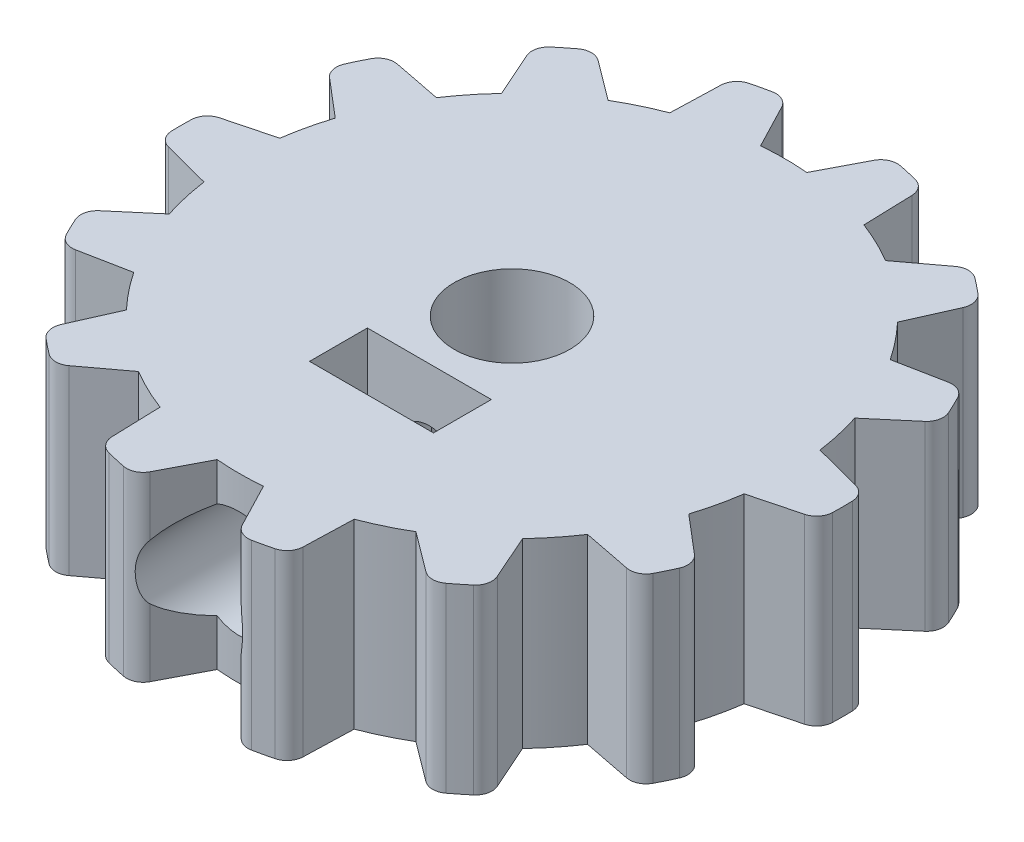
SolidWorks part; units mm, degrees
ref_plane "Front Plane" through (0, 0, 0) normal (0, 0, 1) x (1, 0, 0)
ref_plane "Top Plane" through (0, 0, 0) normal (0, 1, 0) x (1, 0, 0)
ref_plane "Right Plane" through (0, 0, 0) normal (1, 0, 0) x (0, 0, -1)
sketch "Sketch1" plane through (0, 0, 0) normal (0, 1, 0) x (1, 0, 0)
  circle A0 centre (0, 0) radius 20
  dimension "D1" = 40
extrude "Boss-Extrude1" add sketch "Sketch1" along normal blind 11
sketch "Sketch2" plane through (0, 11, 0) normal (0, 1, 0) x (1, 0, 0)
  line L0 (-3.125, 19.7544) -> (-1.3999, 16.4405)
  line L2 (1.3999, 16.4405) -> (3.125, 19.7544)
  circle A0 centre (0, 0) radius 20 construction
  arc A1 (-1.3999, 16.4405) -> (1.3999, 16.4405) centre (0, 0) cw
  arc A2 (3.125, 19.7544) -> (-3.125, 19.7544) centre (0, 0) ccw
  point P6 (0, 16.5)
  dimension "D1" = 16.5
  dimension "D2" = 55
  dimension "D3" = 6.25
extrude "Cut-Extrude1" cut sketch "Sketch2" against normal up to next
fillet "Fillet1" radius 1 2 edges at (3.125, 5.5, -19.7544) (-3.125, 5.5, -19.7544)
pattern_circular "CirPattern1" count 14 over 360 about axis through (0, 11, 0) along (0, -1, 0) of "Cut-Extrude1", "Fillet1"
sketch "Sketch3" plane through (0, 11, 0) normal (0, 1, 0) x (1, 0, 0)
  circle A0 centre (0, 0) radius 3.5
  dimension "D1" = 3.5
extrude "Cut-Extrude2" cut sketch "Sketch3" against normal up to next
sketch "Sketch4" plane through (0, 11, 0) normal (0, 1, 0) x (1, 0, 0)
  line L1 (-3.75, -5) -> (3.75, -5)
  line L2 (-3.75, -5) -> (-3.75, -8.5)
  line L3 (-3.75, -8.5) -> (3.75, -8.5)
  line L4 (3.75, -5) -> (3.75, -8.5)
  point P4 (0, -5)
  dimension "D1" = 5
  dimension "D2" = 3.5
  dimension "D3" = 7.5
extrude "Cut-Extrude3" cut sketch "Sketch4" against normal blind 9
sketch "Sketch6" plane through (0, 0, 0) normal (1, 0, 0) x (0, 0, -1)
  line L0 (0, 5.75) -> (-29.7973, 5.75) construction
  line L1 (-8.5, 2) -> (-5, 2) construction
  line L2 (0, 5.75) -> (0, 7.75)
  line L3 (0, 7.75) -> (-10, 7.75)
  line L4 (-10, 7.75) -> (-10, 9)
  line L5 (-10, 9) -> (-25, 9)
  line L6 (-25, 9) -> (-25, 5.75)
  line L7 (-25, 5.75) -> (0, 5.75)
  dimension "D1" = 3.75
  dimension "D2" = 4
  dimension "D3" = 6.5
  dimension "D4" = 10
  dimension "D5" = 25
revolve "Cut-Revolve1" cut sketch "Sketch6" angle 360 about L0
